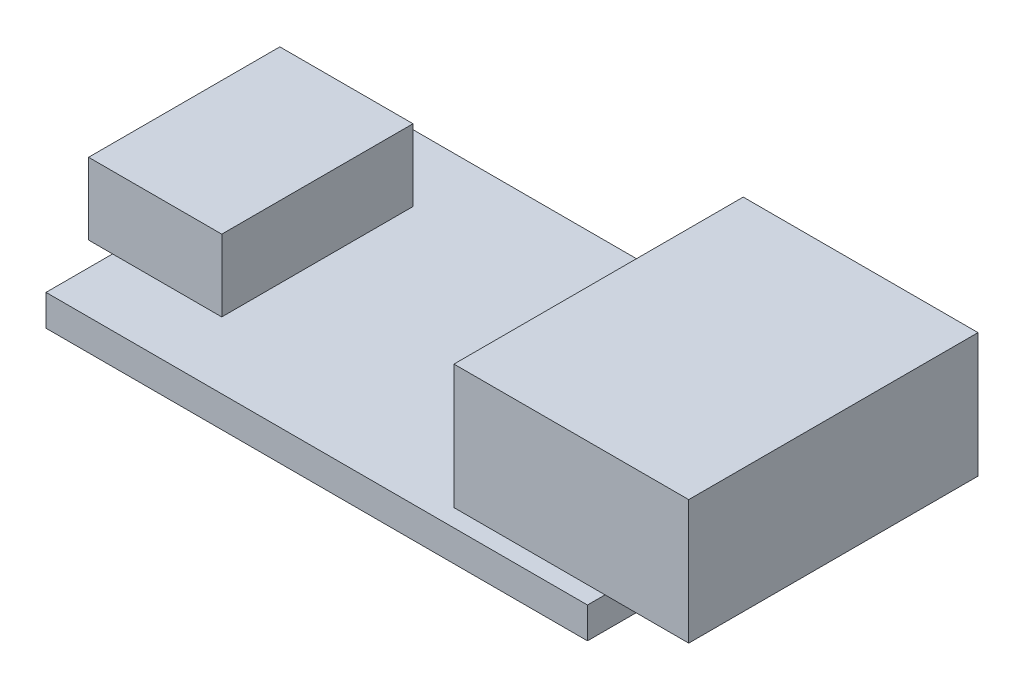
SolidWorks part; units mm, degrees
ref_plane "Front Plane" through (0, 0, 0) normal (0, 0, 1) x (1, 0, 0)
ref_plane "Top Plane" through (0, 0, 0) normal (0, 1, 0) x (1, 0, 0)
ref_plane "Right Plane" through (0, 0, 0) normal (1, 0, 0) x (0, 0, -1)
sketch "Sketch1" plane through (0, 0, 0) normal (0, 1, 0) x (1, 0, 0)
  line L1 (0, 6.785) -> (22.65, 6.785)
  line L2 (0, 6.785) -> (0, -6.785)
  line L3 (0, -6.785) -> (22.65, -6.785)
  line L4 (22.65, 6.785) -> (22.65, -6.785)
  line L5 (0, -55) -> (0, 55) construction
  line L6 (4.5666, 0) -> (0, 0) construction
  line L7 (26.15, 6.05) -> (16.33, 6.05)
  line L8 (26.15, 6.05) -> (26.15, -6.05)
  line L9 (26.15, -6.05) -> (16.33, -6.05)
  line L10 (16.33, 6.05) -> (16.33, -6.05)
  line L11 (-1.0034, 4) -> (4.5666, 4)
  line L12 (-1.0034, 4) -> (-1.0034, -4)
  line L13 (-1.0034, -4) -> (4.5666, -4)
  line L14 (4.5666, 4) -> (4.5666, -4)
  line L15 (22.65, 0) -> (16.33, 0) construction
  line L16 (-55, 0) -> (55, 0) construction
  dimension "D1" = 22.65
  dimension "D2" = 13.57
  dimension "D3" = 9.82
  dimension "D4" = 12.1
  dimension "D5" = 5.57
  dimension "D6" = 8
  dimension "D7" = 3.5
extrude "Boss-Extrude1" add sketch "Sketch1" against normal blind 1.3 contours L1 L4 L3 L2
extrude "Boss-Extrude2" add sketch "Sketch1<3>" along normal blind 5.2 separate body contours L10 L9 L8 L7
sketch "Sketch1<3>" plane through (0, 0, 0) normal (0, 1, 0) x (1, 0, 0) same geometry as "Sketch1"
extrude "Boss-Extrude3" add sketch "Sketch1<4>" along normal blind 3 separate body contours L13 L14 L11 L12
sketch "Sketch1<4>" plane through (0, 0, 0) normal (0, 1, 0) x (1, 0, 0) same geometry as "Sketch1"
